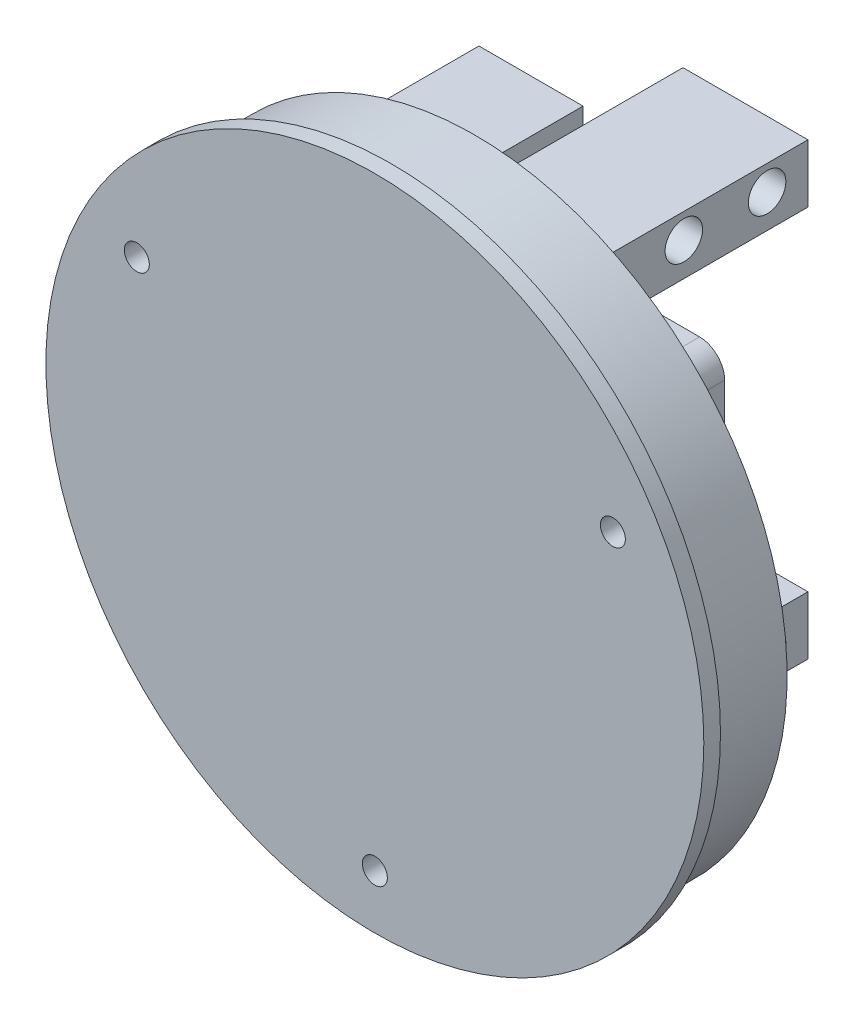
SolidWorks part; units mm, degrees
ref_plane "前视基准面" through (0, 0, 0) normal (0, 0, 1) x (1, 0, 0)
ref_plane "上视基准面" through (0, 0, 0) normal (0, 1, 0) x (1, 0, 0)
ref_plane "右视基准面" through (0, 0, 0) normal (1, 0, 0) x (0, 0, -1)
sketch "草图1" plane through (0, 0, 0) normal (0, 0, 1) x (1, 0, 0)
  circle A0 centre (0, 0) radius 37.5
extrude "凸台-拉伸3" add sketch "草图1" along normal blind 14
sketch "草图2" plane through (0, 0, 0) normal (0, 0, -1) x (-1, 0, 0)
  circle A0 centre (0, 0) radius 37.5
  circle A1 centre (0, 0) radius 39.5
extrude "凸台-拉伸4" add sketch "草图2" against normal blind 2
sketch "草图3" plane through (0, 0, 14) normal (0, 0, 1) x (1, 0, 0)
  circle A0 centre (0, 0) radius 37.5
  circle A1 centre (0, 0) radius 39.5
extrude "凸台-拉伸5" add sketch "草图3" against normal blind 2
sketch "草图4" plane through (0, 0, 0) normal (0, 0, -1) x (-1, 0, 0)
  circle A0 centre (0, 0) radius 39.5
extrude "切除-拉伸1" cut sketch "草图4" against normal blind 2
sketch "草图5" plane through (0, 0, 2) normal (0, 0, -1) x (-1, 0, 0)
  circle A0 centre (0, -33) radius 1.5
  circle A1 centre (-28.5788, 16.5) radius 1.5
  circle A2 centre (28.5788, 16.5) radius 1.5
  point P8 (0, 0)
  dimension "D1" = 3
extrude "切除-拉伸3" cut sketch "草图5" against normal through all
sketch "草图6" plane through (0, 0, 2) normal (0, 0, -1) x (-1, 0, 0)
  line L1 (-20, 20) -> (20, 20)
  line L2 (-20, 20) -> (-20, -20)
  line L3 (-20, -20) -> (20, -20)
  line L4 (20, 20) -> (20, -20)
  line L5 (-20, 20) -> (20, -20) construction
  line L6 (-20, -20) -> (20, 20) construction
extrude "凸台-拉伸6" add sketch "草图6" along normal blind 10
sketch "草图7" plane through (0, 0, 2) normal (0, 0, -1) x (-1, 0, 0)
  line L0 (-10, -20) -> (-10, -27)
  line L1 (20, 20) -> (-20, 20) construction
  line L2 (-10, 20) -> (-10, 27)
  line L3 (-10, 27) -> (5, 27)
  line L4 (5, 27) -> (5, 20)
  line L5 (5, 20) -> (-10, 20)
  line L6 (-20, -20) -> (20, -20) construction
  line L7 (-10, -27) -> (5, -27)
  line L8 (5, -27) -> (5, -20)
  line L9 (5, -20) -> (-10, -20)
extrude "凸台-拉伸7" add sketch "草图7" along normal blind 30
sketch "草图8" plane through (0, 0, -8) normal (0, 0, -1) x (-1, 0, 0)
  line L0 (17, 17) -> (23, 17)
  line L1 (17, 2.8) -> (23, 2.8)
  line L2 (20, 20) -> (20, 17)
  line L3 (20, -20) -> (20, 20) construction
  line L5 (23, 17) -> (23, 2.8)
  line L7 (17, 17) -> (17, 2.8)
  line M5 (20, -20) -> (20, 20)
extrude "凸台-拉伸9" add sketch "草图8" against normal blind 10 contours L5 L0 L1 M5 | L0 L7 L1 M5 region at (-18.5, 9.9, -8) region at (-21.5, 9.9, -8)
sketch "草图9" plane through (0, 0, -8) normal (0, 0, -1) x (-1, 0, 0)
  line L0 (23, 17) -> (17, 17)
  line L1 (17, 17) -> (17, 2.9)
  line L2 (17, 2.9) -> (23, 2.8)
  line L3 (23, 2.8) -> (23, 17)
extrude "凸台-拉伸10" add sketch "草图9" along normal blind 20
sketch "草图10" plane through (-23, 0, 0) normal (-1, 0, 0) x (0, 0, 1)
  circle A0 centre (-17.84, 9.9) radius 1.5
extrude "切除-拉伸4" cut sketch "草图10" against normal blind 20
fillet "圆角1" radius 3 4 edges at (20, 20, -3) (20, -20, -3) (-20, -20, -3) (-20, 20, -3)
sketch "草图11" plane through (-23, 0, 0) normal (-1, 0, 0) x (0, 0, 1)
  line L0 (-28, 17) -> (-6, 17)
  line L1 (2, 17) -> (-28, 17) construction
  line L2 (-6, 17) -> (-6, 2.8)
  line L3 (2, 2.8) -> (-8, 2.8) construction
  line L4 (-6, 2.8) -> (-28, 2.8)
  line L5 (-28, 2.8) -> (-28, 17)
  circle A0 centre (-17.84, 9.9) radius 1.5
extrude "凸台-拉伸11" add sketch "草图11" along normal blind 6.5
chamfer "倒角1" distance 6.5 angle 45 1 edges at (-29.5, 9.9, -6)
sketch "草图12" plane through (-17, 0, 0) normal (1, 0, 0) x (0, 0, -1)
  circle A0 centre (17.84, 9.9) radius 3
extrude "切除-拉伸5" cut sketch "草图12" against normal blind 4
sketch "草图13" plane through (10, 0, 0) normal (1, 0, 0) x (0, 0, -1)
  circle A1 centre (23.1, -24) radius 2.25
  circle A2 centre (13.1, -24) radius 2.25
extrude "切除-拉伸6" cut sketch "草图13" against normal blind 10
sketch "草图15" plane through (10, 0, 0) normal (1, 0, 0) x (0, 0, -1)
  circle A0 centre (23.1, 24) radius 2.25
  circle A1 centre (13.1, 24) radius 2.25
extrude "切除-拉伸7" cut sketch "草图15" against normal blind 10
